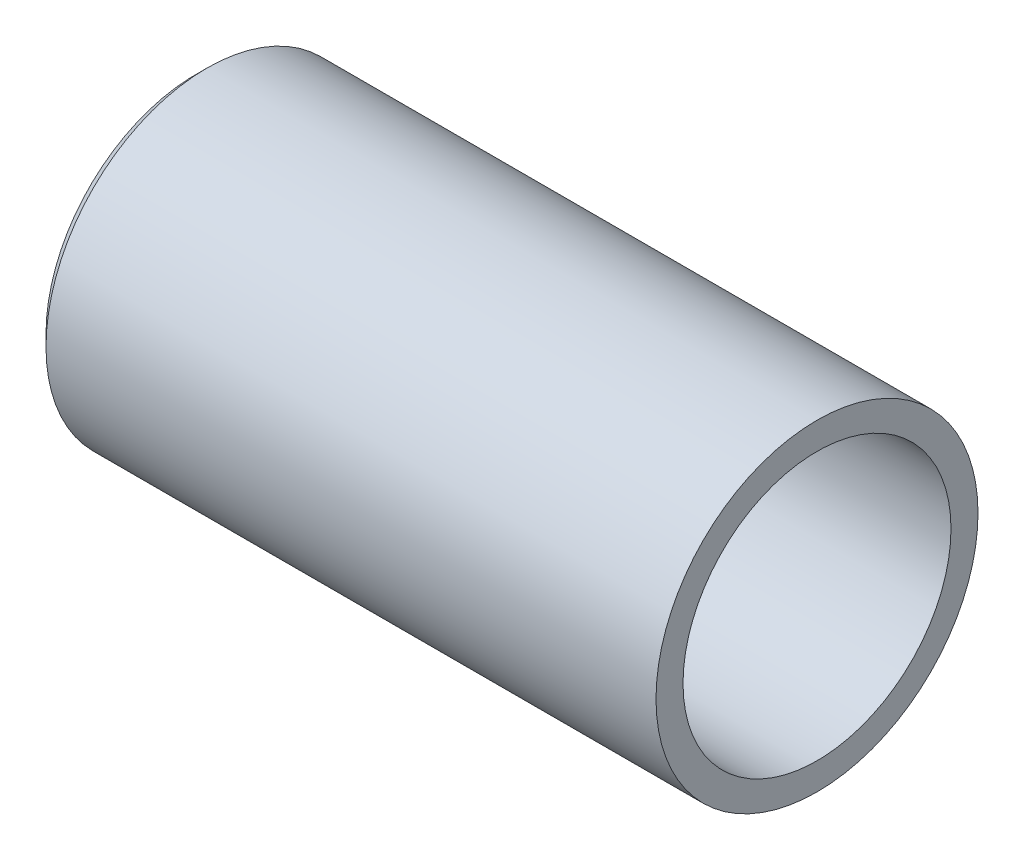
SolidWorks part; units mm, degrees
material "Nylon 6/10"
ref_plane "Front Plane" through (0, 0, 0) normal (0, 0, 1) x (1, 0, 0)
ref_plane "Top Plane" through (0, 0, 0) normal (0, 1, 0) x (1, 0, 0)
ref_plane "Right Plane" through (0, 0, 0) normal (1, 0, 0) x (0, 0, -1)
sketch "Sketch1" plane through (0, 0, 0) normal (0, 0, 1) x (1, 0, 0)
  line L0 (0, 0) -> (22.1407, 0) construction
  line L1 (6.5376, 4.7687) -> (24.6062, 4.7687)
  line L3 (6.2063, 3.9688) -> (24.6063, 3.9688)
  line L4 (24.6062, 4.7687) -> (24.6063, 3.9688)
  line L5 (24.6062, 11.1125) -> (24.6062, -11.1125) construction
  line L7 (6.2063, -4.1672) -> (6.2063, 4.1672) construction
  line L8 (6.2063, 3.9688) -> (6.2063, 4.4374)
  line L9 (6.2063, 4.4374) -> (6.5376, 4.7687)
  point P12 (6.6792, 5.2388)
  dimension "D1" = 7.9375
  dimension "D4" = 45
  dimension "D2" = 0.8
revolve "Revolve1" add sketch "Sketch1" angle 360 about L0
equation "\"D2@Sketch1\"=.8mm"
